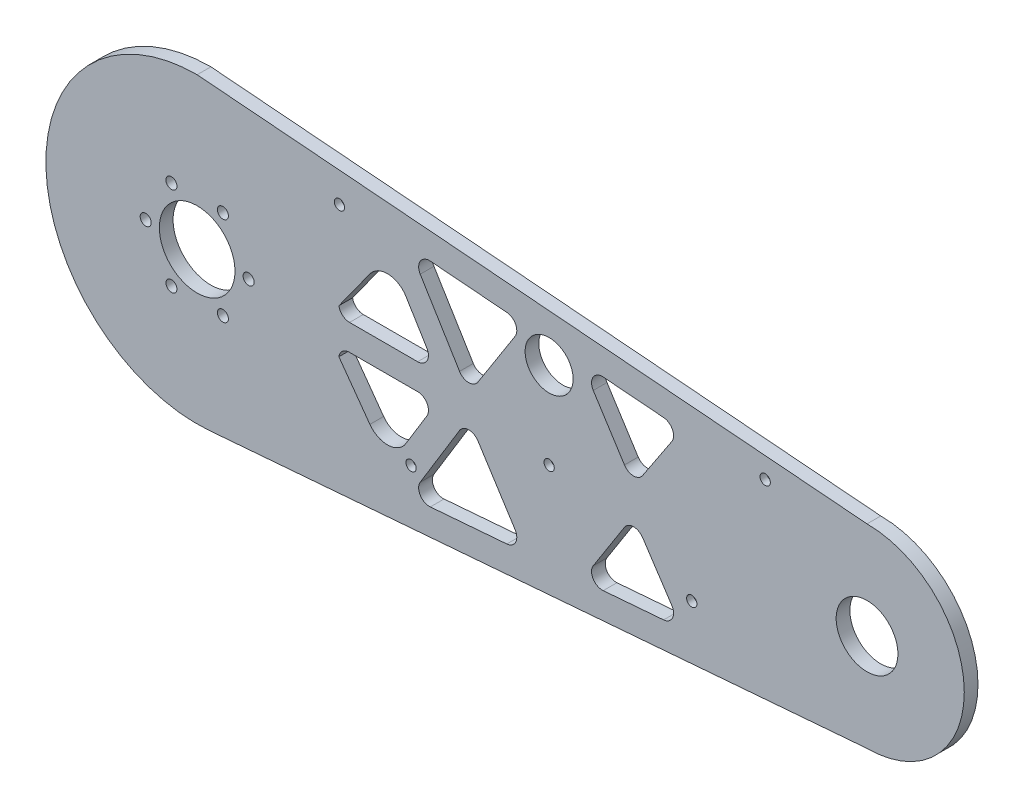
SolidWorks part; units mm, degrees
other "Marca1"
sketch "Croquis3" plane through (-70, -70, 6.35) normal (0, 0, 1) x (1, 0, 0)
material "6061-O (SS)"
ref_plane "Front Plane" through (0, 0, 0) normal (0, 0, 1) x (1, 0, 0)
ref_plane "Top Plane" through (0, 0, 0) normal (0, 1, 0) x (1, 0, 0)
ref_plane "Right Plane" through (0, 0, 0) normal (1, 0, 0) x (0, 0, -1)
sketch "Sketch1" plane through (0, 0, 0) normal (0, 0, 1) x (1, 0, 0)
  line L0 (0, 70) -> (310, 45)
  line L1 (5.1714, -69.8087) -> (310, -45)
  line L2 (0, 0) -> (310, 0) construction
  line L3 (107.899, 49.2595) -> (143.3142, 46.4034)
  line L4 (70.5232, 6) -> (102.03, 6)
  line L5 (219.6238, 32.8105) -> (206.1309, 12.4175)
  line L6 (197.7459, 12.4871) -> (183.2969, 35.1335)
  line L7 (162.8785, 6) -> (162.8785, -6) construction
  line L8 (258.6323, 64.5867) -> (258.6323, 39.5867) construction
  line L9 (147.1275, 38.7303) -> (129.9162, 11.7546)
  line L10 (121.433, 11.8395) -> (103.229, 41.6712)
  line L11 (98.117, 50.0484) -> (42.0027, 50.0484) construction
  line L12 (187.9139, 42.8067) -> (215.8558, 40.5533)
  line L13 (162.8785, 44.8257) -> (162.8785, 6) construction
  line L14 (67.1248, 64.5867) -> (162.8785, 35) construction
  line L15 (201.8849, 6) -> (201.8849, 41.68) construction
  line L16 (125.6066, 5) -> (125.6066, 47.8315) construction
  line L17 (96.5904, 29.5131) -> (106.2981, 13.6045)
  line L18 (125.6066, -5) -> (125.6066, -47.8315) construction
  line L19 (201.8849, -6) -> (201.8849, -41.68) construction
  line L20 (162.8785, -44.8257) -> (162.8785, -6) construction
  line L21 (98.117, -50.0484) -> (42.0027, -50.0484) construction
  line L22 (96.5904, -29.5131) -> (106.2981, -13.6045)
  line L23 (67.1248, 64.5867) -> (409.6974, 64.5867) construction
  line L24 (187.9139, -42.8067) -> (215.8558, -40.5533)
  line L25 (121.433, -11.8395) -> (103.229, -41.6712)
  line L26 (147.1275, -38.7303) -> (129.9162, -11.7546)
  line L27 (162.8785, 0) -> (258.6323, 64.5867) construction
  line L28 (67.1248, 64.5867) -> (67.1248, 39.5867) construction
  line L29 (197.7459, -12.4871) -> (183.2969, -35.1335)
  line L30 (219.6238, -32.8105) -> (206.1309, -12.4175)
  line L31 (70.5232, -6) -> (102.03, -6)
  line L32 (107.899, -49.2595) -> (143.3142, -46.4034)
  line L33 (0, -6.35) -> (0, 6.35) construction
  line L34 (67.1248, 39.5867) -> (162.8785, 35) construction
  line L35 (162.8785, 35) -> (67.6719, 24.0904) construction
  line L36 (79.9417, 30.1512) -> (65.583, 10.2294)
  line L37 (79.9417, -30.1512) -> (65.583, -10.2294)
  arc A0 (65.583, 10.2294) -> (70.5232, 6) centre (70.5232, 11) ccw
  arc A1 (310, -45) -> (310, 45) centre (310, 0) ccw
  circle A2 centre (0, 0) radius 14.2938
  circle A3 centre (310, 0) radius 14.2939
  arc A4 (79.9417, 30.1512) -> (96.5904, 29.5131) centre (88.0542, 24.3041) cw
  arc A5 (96.5904, -29.5131) -> (79.9417, -30.1512) centre (88.0542, -24.3041) cw
  arc A6 (0, 70) -> (5.1714, -69.8087) centre (0, 0) ccw
  arc A7 (187.9139, 42.8067) -> (183.2969, 35.1335) centre (187.512, 37.8229) ccw
  arc A8 (219.6238, 32.8105) -> (215.8558, 40.5533) centre (215.4539, 35.5695) ccw
  arc A9 (206.1309, 12.4175) -> (197.7459, 12.4871) centre (201.961, 15.1765) cw
  circle A10 centre (162.8785, 35) radius 11.1125
  arc A13 (102.03, 6) -> (106.2981, 13.6045) centre (102.03, 11) ccw
  arc A14 (121.433, 11.8395) -> (129.9162, 11.7546) centre (125.7011, 14.444) ccw
  arc A15 (147.1275, 38.7303) -> (143.3142, 46.4034) centre (142.9123, 41.4196) ccw
  arc A16 (107.899, 49.2595) -> (103.229, 41.6712) centre (107.4971, 44.2757) ccw
  arc A17 (107.899, -49.2595) -> (103.229, -41.6712) centre (107.4971, -44.2757) cw
  arc A18 (147.1275, -38.7303) -> (143.3142, -46.4034) centre (142.9123, -41.4196) cw
  arc A19 (121.433, -11.8395) -> (129.9162, -11.7546) centre (125.7011, -14.444) cw
  arc A20 (102.03, -6) -> (106.2981, -13.6045) centre (102.03, -11) cw
  arc A24 (206.1309, -12.4175) -> (197.7459, -12.4871) centre (201.961, -15.1765) ccw
  arc A25 (219.6238, -32.8105) -> (215.8558, -40.5533) centre (215.4539, -35.5695) cw
  arc A26 (187.9139, -42.8067) -> (183.2969, -35.1335) centre (187.512, -37.8229) cw
  arc A29 (65.583, -10.2294) -> (70.5232, -6) centre (70.5232, -11) cw
  point P31 (177.8851, 43.6155)
  point P42 (187.6504, 6)
  point P44 (88.7465, 42.3671)
  point P45 (138.1067, 6)
  point P79 (88.7465, -42.3671)
  point P100 (138.1067, -6)
  point P101 (187.6504, -6)
  point P102 (177.8851, -43.6155)
  point P104 (0, 0)
  point P114 (310, 0)
  point P119 (0.2114, 0.3175)
  dimension "D2" = 45
  dimension "D3" = 12.7
  dimension "D4" = 28.5877
  dimension "D6" = 12
  dimension "D11" = 5
  dimension "D12" = 70
  dimension "D13" = 25
  dimension "D8" = 5
  dimension "D14" = 12
  dimension "D15" = 25
  dimension "D16" = 310
  dimension "D17" = 22.225
  dimension "D5" = 28.5877
  dimension "D19" = 10
  dimension "D20" = 10
  dimension "D7" = 6
  dimension "D9" = 9.279
  dimension "D10" = 34
  dimension "D18" = 35
extrude "Boss-Extrude1" add sketch "Sketch1" along normal blind 6.35
sketch "Sketch2" plane through (0, 0, 6.35) normal (0, 0, 1) x (1, 0, 0)
  line L0 (263.0927, 39.4927) -> (-0.4655, 64.9983)
  line L1 (4.6885, -64.8307) -> (263.1366, -39.5384)
  arc A0 (-0.4655, 64.9983) -> (4.6885, -64.8307) centre (0, 0) ccw
  arc A1 (263.1366, -39.5384) -> (270.3186, -23.7999) centre (262.1626, -29.5859) ccw
  circle A2 centre (0, 0) radius 40
  arc A3 (270.292, 23.7623) -> (270.3186, -23.7999) centre (303.867, 0) ccw
  arc A4 (270.292, 23.7623) -> (263.0927, 39.4927) centre (262.1295, 29.5392) ccw
  dimension "D1" = 10
  dimension "D2" = 41.133
  dimension "D3" = 65
ref_plane "Plane1" through (0, 0, 10) normal (0, 0, 1) x (1, 0, 0)
sketch "Croquis1" plane through (0, 0, 6.35) normal (0, 0, 1) x (1, 0, 0)
  line L0 (5.1714, -69.8087) -> (310, -45) construction
  line L9 (100.6836, -22.8053) -> (88.7465, -42.3671) construction
  line L10 (96.5904, -29.5131) -> (106.2981, -13.6045) construction
  circle A1 centre (98.9956, -37.0901) radius 2.3813
  circle A2 centre (228.8774, -26.5196) radius 2.3813
  point P20 (0, 0)
  dimension "D5" = 4.7625
  dimension "D1" = 4.7625
extrude "Cortar-Extruir1" cut sketch "Croquis1" against normal blind 50
sketch "Croquis2" plane through (0, 0, 6.35) normal (0, 0, 1) x (1, 0, 0)
  circle A0 centre (98.9956, -37.0901) radius 5
  circle A1 centre (228.8774, -26.5196) radius 5
  dimension "D1" = 10
sketch "Croquis4" plane through (0, 0, 6.35) normal (0, 0, 1) x (1, 0, 0)
  line L0 (162.8785, 35) -> (162.8785, -45) construction
  line L1 (135.7539, -45) -> (190.0032, -45) construction
  circle A0 centre (162.8785, -5) radius 5
  point P8 (162.8785, -45)
  dimension "D1" = 10
  dimension "D2" = 40
sketch "Croquis6" plane through (0, 0, 6.35) normal (0, 0, 1) x (1, 0, 0)
  line L0 (98.9956, -37.0901) -> (228.8774, -26.5196) construction
  line L1 (228.8774, -26.5196) -> (262.8716, 39.2101) construction
  line L2 (98.9956, -37.0901) -> (65.8414, 50.869) construction
  circle A0 centre (65.8414, 50.869) radius 2.3813
  circle A1 centre (262.8716, 39.2101) radius 2.3813
  dimension "D5" = 4.7625
  dimension "D1" = 94
  dimension "D2" = 74
  dimension "D3" = 106
  dimension "D4" = 238
extrude "Cortar-Extruir6" cut sketch "Croquis6" against normal blind 10
sketch "Croquis7" plane through (0, 0, 6.35) normal (0, 0, 1) x (1, 0, 0)
  circle A0 centre (65.8414, 50.869) radius 5
  circle A1 centre (262.8716, 39.2101) radius 5
  dimension "D1" = 10
sketch "Croquis8" plane through (0, 0, 6.35) normal (0, 0, 1) x (1, 0, 0)
  circle A0 centre (0, 0) radius 17.5
  dimension "D1" = 35
extrude "Cortar-Extruir8" cut sketch "Croquis8" against normal blind 10
sketch "Croquis9" plane through (0, 0, 0) normal (0, 0, -1) x (-1, 0, 0)
  line L0 (0, 0) -> (23.8125, 0) construction
  circle A0 centre (0, 0) radius 23.8125 construction
  circle A1 centre (23.8125, 0) radius 2.5527
  circle A2 centre (11.9062, -20.6222) radius 2.5527
  circle A3 centre (-11.9063, -20.6222) radius 2.5527
  circle A4 centre (-23.8125, 0) radius 2.5527
  circle A5 centre (-11.9062, 20.6222) radius 2.5527
  circle A6 centre (11.9063, 20.6222) radius 2.5527
  point P17 (0, 0)
  dimension "D1" = 47.625
  dimension "D2" = 5.1054
  dimension "D3" = 6
extrude "Cortar-Extruir9" cut sketch "Croquis9" against normal blind 10
sketch "Croquis5" plane through (0, 0, 6.35) normal (0, 0, 1) x (1, 0, 0)
  circle A0 centre (162.8785, -5) radius 2.3813
  dimension "D1" = 4.7625
extrude "Cortar-Extruir5" cut sketch "Croquis5" against normal blind 10
sketch "Croquis10" plane through (0, 0, 0) normal (0, 0, -1) x (-1, 0, 0)
  circle A0 centre (-262.8716, 39.2101) radius 5
  circle A1 centre (-65.8414, 50.869) radius 5
  circle A2 centre (-162.8785, -5) radius 5
  circle A3 centre (-228.8774, -26.5196) radius 5
  circle A4 centre (-98.9956, -37.0901) radius 5
extrude "Cortar-Extruir10" cut sketch "Croquis10" against normal blind 3.18
